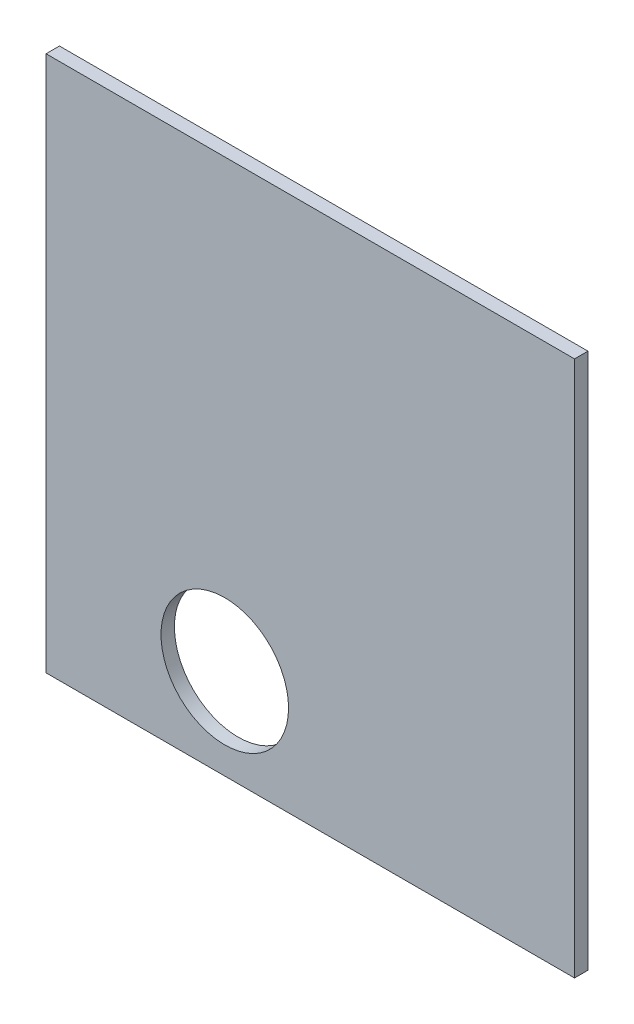
SolidWorks part; units mm, degrees
ref_plane "Front Plane" through (0, 0, 0) normal (0, 0, 1) x (1, 0, 0)
ref_plane "Top Plane" through (0, 0, 0) normal (0, 1, 0) x (1, 0, 0)
ref_plane "Right Plane" through (0, 0, 0) normal (1, 0, 0) x (0, 0, -1)
sketch "Sketch1" plane through (0, 0, 0) normal (0, 0, 1) x (1, 0, 0)
  line L1 (0, 0) -> (118.28, 0)
  line L2 (0, 0) -> (0, 120)
  line L3 (0, 120) -> (118.28, 120)
  line L4 (118.28, 0) -> (118.28, 120)
  dimension "D1" = 118.28
  dimension "D2" = 120
extrude "Boss-Extrude1" add sketch "Sketch1" along normal blind 3
sketch "Sketch2" plane through (0, 0, 3) normal (0, 0, 1) x (1, 0, 0)
  line L0 (118.28, 120) -> (0, 120) construction
  line L2 (0, 120) -> (0, 0) construction
  circle A0 centre (40, 20.31) radius 14.275
  dimension "D1" = 28.55
  dimension "D2" = 40
  dimension "D3" = 99.69
extrude "Cut-Extrude1" cut sketch "Sketch2" against normal blind 3
